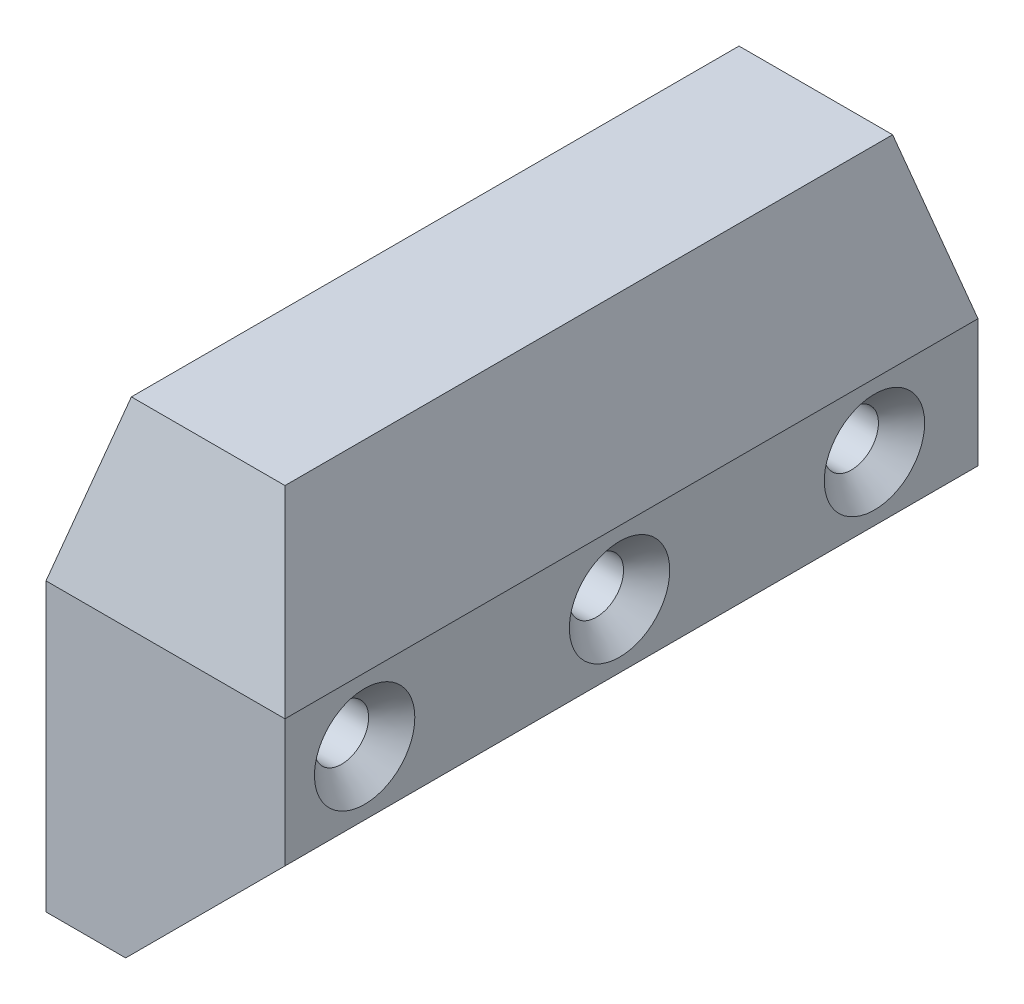
SolidWorks part; units mm, degrees
ref_plane "Plan de face" through (0, 0, 0) normal (0, 0, 1) x (1, 0, 0)
ref_plane "Plan de dessus" through (0, 0, 0) normal (0, 1, 0) x (1, 0, 0)
ref_plane "Plan de droite" through (0, 0, 0) normal (1, 0, 0) x (0, 0, -1)
sketch "Main-Sketch" plane through (0, 0, 0) normal (0, 0, 1) x (1, 0, 0)
  line L0 (0, 8) -> (2.6795, 18)
  line L1 (0, 0) -> (15, 0)
  line L2 (0, 0) -> (0, 8)
  line L3 (2.6795, 18) -> (12.3205, 18)
  line L4 (15, 0) -> (15, 8)
  line L5 (12.3205, 18) -> (15, 8)
  dimension "D1" = 15
  dimension "D2" = 8
  dimension "D3" = 165
  dimension "D4" = 10
extrude "Main-Extrusion" add sketch "Main-Sketch" along normal blind 43.5
ref_plane "Plan-Left" through (0, 11.4109, 42.5861) normal (0, 0.2588, 0.9659) x (-1, 0, 0)
ref_axis "Axe1" through (18.571, 18, 40.8205) along (-1, 0, 0)
sketch "Left-Sketch" plane through (0, 11.4109, 42.5861) normal (0, 0.2588, 0.9659) x (-1, 0, 0)
  line L1 (0, 3.5312) -> (-15, 3.5312)
  line L2 (0, 3.5312) -> (0, -6.8215)
  line L3 (0, -6.8215) -> (-15, -6.8215)
  line L4 (-15, 3.5312) -> (-15, -6.8215)
  line L5 (-18.571, -6.8215) -> (0.4485, -6.8215) construction
extrude "Left-Hole" cut sketch "Left-Sketch" along normal through all
ref_plane "Plan-Right" through (0, 0.5359, -2) normal (0, 0.2588, -0.9659) x (-1, 0, 0)
ref_axis "Axe2" through (12.3205, 18, 2.6795) along (-1, 0, 0)
sketch "Right-Sketch" plane through (0, 0.5359, -2) normal (0, 0.2588, -0.9659) x (-1, 0, 0)
  line L0 (-12.3205, 18.0802) -> (-2.6795, 18.0802) construction
  line L1 (-15, 7.7274) -> (0, 7.7274)
  line L2 (-15, 7.7274) -> (-15, 18.0802)
  line L3 (-15, 18.0802) -> (0, 18.0802)
  line L4 (0, 7.7274) -> (0, 18.0802)
extrude "Right-Hole" cut sketch "Right-Sketch" along normal through all
sketch "Bottom-Sketch" plane through (0, 0, 0) normal (0, 0, 1) x (1, 0, 0)
  line L0 (0, -10) -> (5, -10)
  line L1 (0, 0) -> (15, 0)
  line L2 (0, 0) -> (0, -10)
  line L3 (5, -10) -> (15, 0)
  line L4 (15, 0) -> (15, 8) construction
  dimension "D1" = 135
  dimension "D2" = 5
extrude "Bottom-Hole" add sketch "Bottom-Sketch" along normal up to surface (43.5 mm away) up to face at (7.5, 4, 43.5)
hole_wizard "Fraisage pour vis à tête fraisée M31" positions "Esquisse7" profile "Esquisse6" countersink size "M3" standard "Ansi Metric" end condition through all
sketch "Esquisse7" plane through (15, 0, 0) normal (1, 0, 0) x (0, 0, -1)
  line L0 (-43.5, 0) -> (-43.5, 8) construction
  point P0 (-38.5, 4)
  point P13 (-43.5, 4)
  dimension "D1" = 5
sketch "Esquisse6" plane through (15, 4, 38.5) normal (0, 1, 0) x (0, 0, -1)
  line L0 (0, 0) -> (0, 15)
  line L1 (0, 15) -> (1.7, 15)
  line L2 (1.7, 15) -> (1.7, 1.45)
  line L3 (1.7, 1.45) -> (3.15, 0)
  line L5 (3.15, 0) -> (0, 0)
  line L6 (-1.7, 1.45) -> (-3.15, 0) construction
  line L11 (0, -6.35) -> (0, 107.95) construction
  dimension "Diamètre du perçage jusqu'au prochain" = 3.4
  dimension "Profondeur du perçage jusqu'au prochain" = 15
  dimension "Diamètre du fraisage entrant" = 6.3
  dimension "Angle du fraisage entrant" = 90
pattern_linear "Répétition linéaire1" count 3 spacing 16 along (0, 0, -1) of "Fraisage pour vis à tête fraisée M31"
